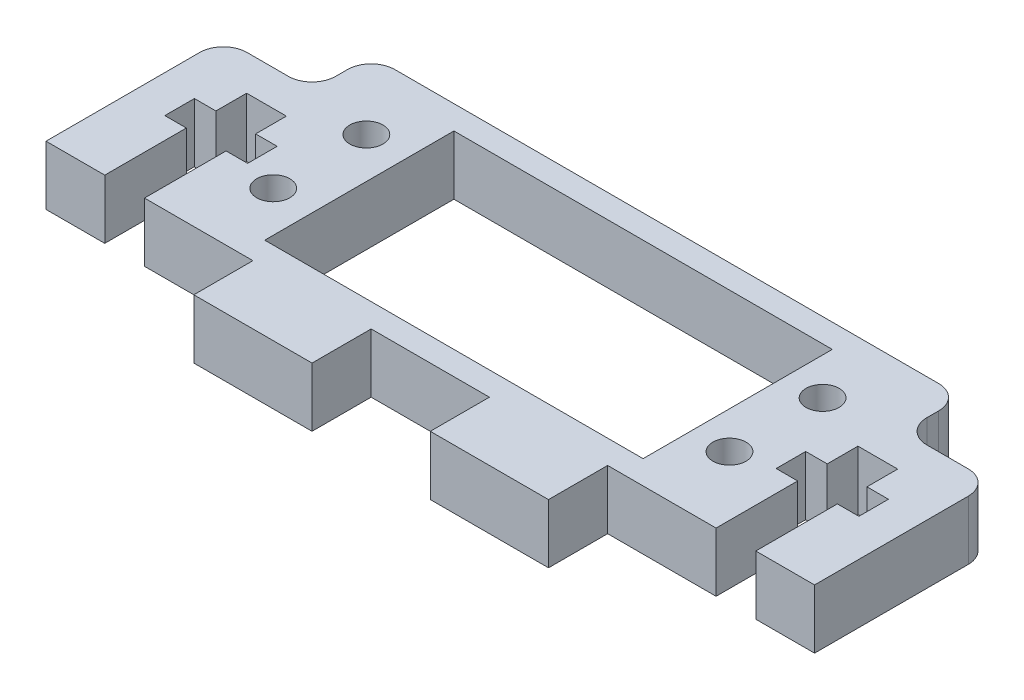
SolidWorks part; units mm, degrees
ref_plane "Front Plane" through (0, 0, 0) normal (0, 0, 1) x (1, 0, 0)
ref_plane "Top Plane" through (0, 0, 0) normal (0, 1, 0) x (1, 0, 0)
ref_plane "Right Plane" through (0, 0, 0) normal (1, 0, 0) x (0, 0, -1)
sketch "Sketch1" plane through (0, 0, 0) normal (0, 1, 0) x (1, 0, 0)
  line L0 (0, 0) -> (0, 13.5231) construction
  line L1 (-31.75, 12.7) -> (31.75, 12.7)
  line L2 (-31.75, 12.7) -> (-31.75, -12.7)
  line L3 (-31.75, -12.7) -> (-19.05, -12.7)
  line L4 (31.75, 12.7) -> (31.75, -12.7)
  line L5 (0, 0) -> (26.1056, 0) construction
  line L6 (-6.35, -12.7) -> (6.35, -12.7)
  line L7 (19.05, -12.7) -> (31.75, -12.7)
  line L8 (-19.05, -12.7) -> (-19.05, -19.05)
  line L9 (-19.05, -19.05) -> (-6.35, -19.05)
  line L10 (-6.35, -12.7) -> (-6.35, -19.05)
  line L12 (6.35, -12.7) -> (6.35, -19.05)
  line L13 (6.35, -19.05) -> (19.05, -19.05)
  line L14 (19.05, -12.7) -> (19.05, -19.05)
  line L15 (-20.32, 10.16) -> (20.32, 10.16)
  line L16 (-20.32, 10.16) -> (-20.32, -10.16)
  line L17 (-20.32, -10.16) -> (20.32, -10.16)
  line L18 (20.32, 10.16) -> (20.32, -10.16)
  dimension "D1" = 6.35
  dimension "D2" = 6.35
  dimension "D3" = 12.7
  dimension "D4" = 12.7
  dimension "D5" = 12.7
  dimension "D6" = 63.5
  dimension "D7" = 25.4
  dimension "D8" = 20.32
  dimension "D9" = 40.64
extrude "Boss-Extrude1" add sketch "Sketch1" along normal blind 6.35
sketch "Sketch2" plane through (0, 6.35, 0) normal (0, 1, 0) x (1, 0, 0)
  circle A0 centre (-24.6905, 5.127) radius 1.778
  circle A1 centre (-24.6905, -4.873) radius 1.778
  circle A2 centre (24.3095, 5.127) radius 1.778
  circle A3 centre (24.3095, -4.873) radius 1.778
  arc A4 (-25.9348, 3.857) -> (-25.9348, 6.397) centre (-24.6905, 5.127) ccw construction
  arc A5 (-25.9348, -6.143) -> (-25.9348, -3.603) centre (-24.6905, -4.873) ccw construction
  arc A6 (25.5538, 6.397) -> (25.5538, 3.857) centre (24.3095, 5.127) ccw construction
  arc A7 (25.5538, -3.603) -> (25.5538, -6.143) centre (24.3095, -4.873) ccw construction
extrude "Cut-Extrude1" cut sketch "Sketch2" against normal through all
sketch "Sketch3" plane through (0, 6.35, 0) normal (0, 1, 0) x (1, 0, 0)
  line L0 (-31.75, 12.7) -> (-31.75, -12.7) construction
  line L1 (-31.75, 6.35) -> (-41.275, 6.35)
  line L2 (-31.75, 6.35) -> (-31.75, -12.7)
  line L3 (-31.75, -12.7) -> (-41.275, -12.7)
  line L4 (-41.275, 6.35) -> (-41.275, -12.7)
  line L5 (31.75, -12.7) -> (31.75, 12.7) construction
  line L6 (31.75, 6.35) -> (41.275, 6.35)
  line L7 (31.75, 6.35) -> (31.75, -12.7)
  line L8 (31.75, -12.7) -> (41.275, -12.7)
  line L9 (41.275, 6.35) -> (41.275, -12.7)
  line L11 (-31.75, -12.7) -> (-19.05, -12.7) construction
  dimension "D1" = 9.525
  dimension "D2" = 19.05
extrude "Boss-Extrude2" add sketch "Sketch3" against normal up to surface (6.35 mm away) up to face at (24.3095, 0, 6.651)
sketch "Sketch4" plane through (0, 6.35, 0) normal (0, 1, 0) x (1, 0, 0)
  line L2 (-41.275, -12.7) -> (-19.05, -12.7) construction
  line L3 (-41.275, 6.35) -> (-41.275, -12.7) construction
  line L4 (19.05, -12.7) -> (41.275, -12.7) construction
  line L5 (41.275, -12.7) -> (41.275, 6.35) construction
  line B0 (-34.9636, -12.7) -> (-30.6964, -12.7)
  line B1 (-30.6964, -0.762) -> (-28.385, -0.762)
  line B2 (-28.385, -0.762) -> (-28.385, -3.937)
  line B3 (-28.385, -3.937) -> (-30.6964, -3.937)
  line B4 (-30.6964, -3.937) -> (-30.6964, -12.7)
  line B5 (-30.6964, -0.762) -> (-30.6964, 2.54)
  line B6 (-30.6964, 2.54) -> (-34.9636, 2.54)
  line B7 (-34.9636, -0.762) -> (-34.9636, 2.54)
  line B8 (-34.9636, -3.937) -> (-34.9636, -12.7)
  line B9 (-37.275, -3.937) -> (-34.9636, -3.937)
  line B10 (-37.275, -0.762) -> (-37.275, -3.937)
  line B11 (-34.9636, -0.762) -> (-37.275, -0.762)
  line B12 (30.6964, -12.7) -> (34.9636, -12.7)
  line B13 (34.9636, -0.762) -> (37.275, -0.762)
  line B14 (37.275, -0.762) -> (37.275, -3.937)
  line B15 (37.275, -3.937) -> (34.9636, -3.937)
  line B16 (34.9636, -3.937) -> (34.9636, -12.7)
  line B17 (34.9636, -0.762) -> (34.9636, 2.54)
  line B18 (34.9636, 2.54) -> (30.6964, 2.54)
  line B19 (30.6964, -0.762) -> (30.6964, 2.54)
  line B20 (30.6964, -3.937) -> (30.6964, -12.7)
  line B21 (28.385, -3.937) -> (30.6964, -3.937)
  line B22 (28.385, -0.762) -> (28.385, -3.937)
  line B23 (30.6964, -0.762) -> (28.385, -0.762)
  dimension "D1" = 4
  dimension "D2" = 4
sketch_block_instance "TSlot-1"
sketch_block "TSlot" parameters "D1"=3.302, "D2"=3.175
sketch_block_instance "TSlot-3" parameters "D1"=19.05, "D2"=3.6932
extrude "Cut-Extrude2" cut sketch "Sketch4" against normal through all
fillet "Fillet1" radius 2.54 6 edges at (-31.75, 3.175, -12.7) (31.75, 3.175, -12.7) (41.275, 3.175, -6.35) (-41.275, 3.175, -6.35)
